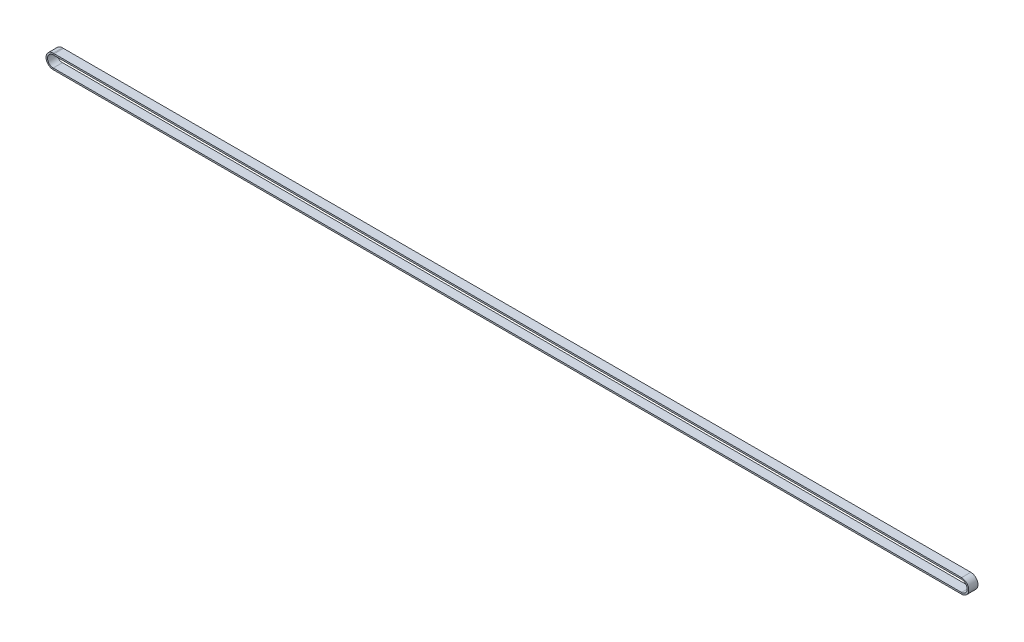
SolidWorks part; units mm, degrees
ref_plane "Front Plane" through (0, 0, 0) normal (0, 0, 1) x (1, 0, 0)
ref_plane "Top Plane" through (0, 0, 0) normal (0, 1, 0) x (1, 0, 0)
ref_plane "Right Plane" through (0, 0, 0) normal (1, 0, 0) x (0, 0, -1)
sketch "Sketch2" plane through (0, 0, 0) normal (0, 0, 1) x (1, 0, 0)
  line L0 (0, 0) -> (1, 0) construction
  line L1 (0, 0) -> (0, 1) construction
  line L2 (-1, -33.342) -> (883.5208, -33.342)
  line L3 (883.5208, -47.342) -> (-1, -47.342)
  arc A0 (-1, -47.342) -> (-1, -33.342) centre (-1, -40.342) cw
  arc A1 (883.5208, -33.342) -> (883.5208, -47.342) centre (883.5208, -40.342) cw
sketch "Sketch3" plane through (0, 0, 0) normal (1, 0, 0) x (0, 0, -1)
  line L1 (0, -34.842) -> (-9, -34.842)
  line L2 (0, -34.842) -> (0, -33.342)
  line L3 (0, -33.342) -> (-9, -33.342)
  line L4 (-9, -34.842) -> (-9, -33.342)
  dimension "D1" = 9
  dimension "D2" = 1.5
sweep "Sweep1" add profiles "Sketch3" path "Sketch2"
